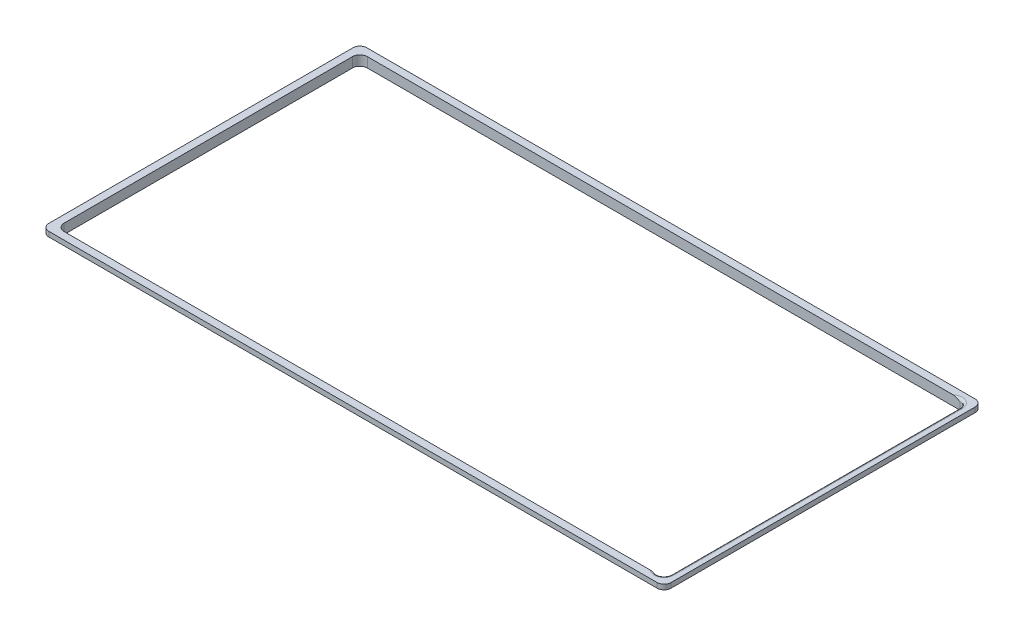
SolidWorks part; units mm, degrees
ref_plane "Ebene vorne" through (0, 0, 0) normal (0, 0, 1) x (1, 0, 0)
ref_plane "Ebene oben" through (0, 0, 0) normal (0, 1, 0) x (1, 0, 0)
ref_plane "Ebene rechts" through (0, 0, 0) normal (1, 0, 0) x (0, 0, -1)
sketch "Skizze1" plane through (0, 0, 0) normal (0, 1, 0) x (1, 0, 0)
  line L0 (6.2, -3.2) -> (245.8, -3.2)
  line L1 (3, 0) -> (249, 0)
  line L2 (0, -3) -> (0, -126)
  line L3 (3, -129) -> (249, -129)
  line L4 (252, -3) -> (252, -126)
  line L5 (0, 0) -> (252, -129) construction
  line L6 (0, -129) -> (252, 0) construction
  line L7 (248.8, -6.2) -> (248.8, -122.8)
  line L8 (6.2, -125.8) -> (245.8, -125.8)
  line L9 (3.2, -6.2) -> (3.2, -122.8)
  line L10 (0, 0) -> (252, 0) construction
  line L11 (252, 0) -> (252, -129) construction
  line L12 (0, -129) -> (252, -129) construction
  line L13 (0, 0) -> (0, -129) construction
  line L14 (3.2, -3.2) -> (248.8, -3.2) construction
  line L15 (248.8, -3.2) -> (248.8, -125.8) construction
  line L16 (3.2, -125.8) -> (248.8, -125.8) construction
  line L17 (3.2, -3.2) -> (3.2, -125.8) construction
  arc A0 (249, 0) -> (252, -3) centre (249, -3) cw
  arc A1 (249, -129) -> (252, -126) centre (249, -126) ccw
  arc A2 (0, -126) -> (3, -129) centre (3, -126) ccw
  arc A3 (3, 0) -> (0, -3) centre (3, -3) ccw
  arc A4 (245.8, -3.2) -> (248.8, -6.2) centre (245.8, -6.2) cw
  arc A5 (248.8, -122.8) -> (245.8, -125.8) centre (245.8, -122.8) cw
  arc A6 (6.2, -125.8) -> (3.2, -122.8) centre (6.2, -122.8) cw
  arc A7 (6.2, -3.2) -> (3.2, -6.2) centre (6.2, -6.2) ccw
  point P4 (126, -64.5)
  dimension "D4" = 3
  dimension "D5" = 3
  dimension "D1" = 252
  dimension "D2" = 129
  dimension "D3" = 3.2
extrude "Aufsatz-Linear austragen1" add sketch "Skizze1" along normal blind 2
sketch "Skizze2" plane through (0, 0, 0) normal (0, -1, 0) x (1, 0, 0)
  line L0 (248.8, 122.8) -> (248.8, 6.2) construction
  line L1 (245.8, 3.2) -> (6.2, 3.2) construction
  line L2 (3.2, 6.2) -> (3.2, 122.8) construction
  line L3 (6.2, 125.8) -> (245.8, 125.8) construction
  line L4 (248.8, 122.8) -> (248.8, 6.2)
  line L5 (245.8, 3.2) -> (6.2, 3.2)
  line L6 (3.2, 6.2) -> (3.2, 122.8)
  line L7 (6.2, 125.8) -> (245.8, 125.8)
  line L8 (6.2, 126.8) -> (245.8, 126.8)
  line L9 (249.8, 122.8) -> (249.8, 6.2)
  line L10 (245.8, 2.2) -> (6.2, 2.2)
  line L11 (2.2, 6.2) -> (2.2, 122.8)
  arc A0 (248.8, 122.8) -> (245.8, 125.8) centre (245.8, 122.8) ccw construction
  arc A1 (245.8, 3.2) -> (248.8, 6.2) centre (245.8, 6.2) ccw construction
  arc A2 (3.2, 6.2) -> (6.2, 3.2) centre (6.2, 6.2) ccw construction
  arc A3 (6.2, 125.8) -> (3.2, 122.8) centre (6.2, 122.8) ccw construction
  arc A4 (248.8, 122.8) -> (245.8, 125.8) centre (245.8, 122.8) ccw
  arc A5 (245.8, 3.2) -> (248.8, 6.2) centre (245.8, 6.2) ccw
  arc A6 (3.2, 6.2) -> (6.2, 3.2) centre (6.2, 6.2) ccw
  arc A7 (6.2, 125.8) -> (3.2, 122.8) centre (6.2, 122.8) ccw
  arc A8 (249.8, 122.8) -> (245.8, 126.8) centre (245.8, 122.8) ccw
  arc A9 (245.8, 2.2) -> (249.8, 6.2) centre (245.8, 6.2) ccw
  arc A10 (2.2, 6.2) -> (6.2, 2.2) centre (6.2, 6.2) ccw
  arc A11 (6.2, 126.8) -> (2.2, 122.8) centre (6.2, 122.8) ccw
  dimension "D1" = 1
extrude "Aufsatz-Linear austragen2" add sketch "Skizze2" along normal blind 2
sketch "Skizze3" plane through (0, 2, 0) normal (0, 1, 0) x (1, 0, 0)
  line L0 (249, -0.2) -> (3, -0.2)
  line L1 (0.2, -3) -> (0.2, -126)
  line L2 (3, -128.8) -> (249, -128.8)
  line L3 (251.8, -126) -> (251.8, -3)
  line L4 (249, 0) -> (3, 0)
  line L5 (0, -3) -> (0, -126)
  line L6 (3, -129) -> (249, -129)
  line L7 (252, -126) -> (252, -3)
  line L8 (249, 0) -> (3, 0)
  line L9 (0, -3) -> (0, -126)
  line L10 (3, -129) -> (249, -129)
  line L11 (252, -126) -> (252, -3)
  arc A0 (3, -0.2) -> (0.2, -3) centre (3, -3) ccw
  arc A1 (0.2, -126) -> (3, -128.8) centre (3, -126) ccw
  arc A2 (249, -128.8) -> (251.8, -126) centre (249, -126) ccw
  arc A3 (251.8, -3) -> (249, -0.2) centre (249, -3) ccw
  arc A4 (252, -3) -> (249, 0) centre (249, -3) ccw
  arc A5 (3, 0) -> (0, -3) centre (3, -3) ccw
  arc A6 (0, -126) -> (3, -129) centre (3, -126) ccw
  arc A7 (249, -129) -> (252, -126) centre (249, -126) ccw
  arc A8 (252, -3) -> (249, 0) centre (249, -3) ccw
  arc A9 (3, 0) -> (0, -3) centre (3, -3) ccw
  arc A10 (0, -126) -> (3, -129) centre (3, -126) ccw
  arc A11 (249, -129) -> (252, -126) centre (249, -126) ccw
  dimension "D1" = 0
  dimension "D2" = 0.2
extrude "Schnitt-Linear austragen1" cut sketch "Skizze3" against normal blind 34
fillet "Verrundung2" radius 1 3 edges at (247.9213, 2, 4.0787) (247.9213, 2, 124.9213) (248.8, 2, 64.5) tangent propagation no
